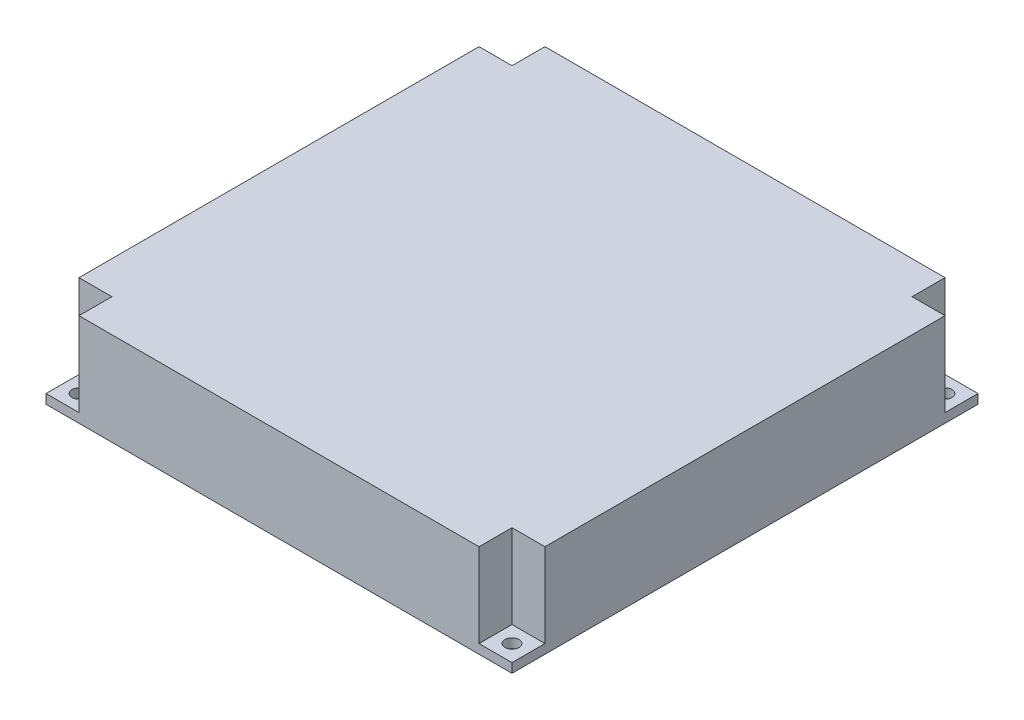
SolidWorks part; units mm, degrees
ref_plane "Alzado" through (0, 0, 0) normal (0, 0, 1) x (1, 0, 0)
ref_plane "Planta" through (0, 0, 0) normal (0, 1, 0) x (1, 0, 0)
ref_plane "Vista lateral" through (0, 0, 0) normal (1, 0, 0) x (0, 0, -1)
sketch "Croquis1" plane through (0, 0, 0) normal (0, 1, 0) x (1, 0, 0)
  line L1 (-50, 50) -> (50, 50)
  line L2 (-50, 50) -> (-50, -50)
  line L3 (-50, -50) -> (50, -50)
  line L4 (50, 50) -> (50, -50)
  line L5 (-50, 50) -> (50, -50) construction
  line L6 (-50, -50) -> (50, 50) construction
  point P0 (0, 0)
  dimension "D1" = 100
  dimension "D2" = 100
extrude "Saliente-Extruir1" add sketch "Croquis1" along normal blind 20
sketch "Croquis2" plane through (0, 20, 0) normal (0, 1, 0) x (1, 0, 0)
  line L0 (-50, -50) -> (50, 50) construction
  line L1 (-50, 50) -> (50, -50) construction
  circle A0 centre (-46.4645, -46.4645) radius 1.5
  circle A1 centre (-46.4645, 46.4645) radius 1.5
  circle A2 centre (46.4645, 46.4645) radius 1.5
  circle A3 centre (46.4645, -46.4645) radius 1.5
  point P19 (0, 0)
  dimension "D1" = 3
  dimension "D2" = 5
  dimension "D3" = 4
extrude "Cortar-Extruir1" cut sketch "Croquis2" against normal blind 28
sketch "Croquis3" plane through (0, 20, 0) normal (0, 1, 0) x (1, 0, 0)
  line L0 (-42.9289, 42.9289) -> (-50, 50) construction
  line L1 (-42.9289, -42.9289) -> (-50, -42.9289)
  line L2 (-42.9289, -42.9289) -> (-42.9289, -50)
  line L3 (-42.9289, -50) -> (-50, -50)
  line L4 (-50, -42.9289) -> (-50, -50)
  line L5 (-42.9289, -42.9289) -> (-50, -50) construction
  line L6 (-42.9289, -50) -> (-50, -42.9289) construction
  line L7 (-50, 42.9289) -> (-42.9289, 50) construction
  line L8 (-42.9289, 42.9289) -> (-50, 42.9289)
  line L9 (-42.9289, 42.9289) -> (-42.9289, 50)
  line L10 (-42.9289, 50) -> (-50, 50)
  line L11 (-50, 42.9289) -> (-50, 50)
  line L12 (42.9289, 42.9289) -> (50, 50) construction
  line L13 (42.9289, 50) -> (50, 42.9289) construction
  line L14 (42.9289, 42.9289) -> (42.9289, 50)
  line L15 (42.9289, 42.9289) -> (50, 42.9289)
  line L16 (50, 42.9289) -> (50, 50)
  line L17 (42.9289, 50) -> (50, 50)
  line L18 (42.9289, -42.9289) -> (50, -50) construction
  line L19 (50, -42.9289) -> (42.9289, -50) construction
  line L20 (42.9289, -42.9289) -> (50, -42.9289)
  line L21 (42.9289, -42.9289) -> (42.9289, -50)
  line L22 (42.9289, -50) -> (50, -50)
  line L23 (50, -42.9289) -> (50, -50)
  point P0 (-46.4645, -46.4645)
  point P10 (-46.4645, 46.4645)
  point P15 (46.4645, 46.4645)
  point P20 (46.4645, -46.4645)
  point P25 (0, 0)
  dimension "D1" = 4
extrude "Cortar-Extruir2" cut sketch "Croquis3" against normal blind 18
shell "Vaciado1" thickness 2 removed face at (46.4645, 0, 47.9645)
